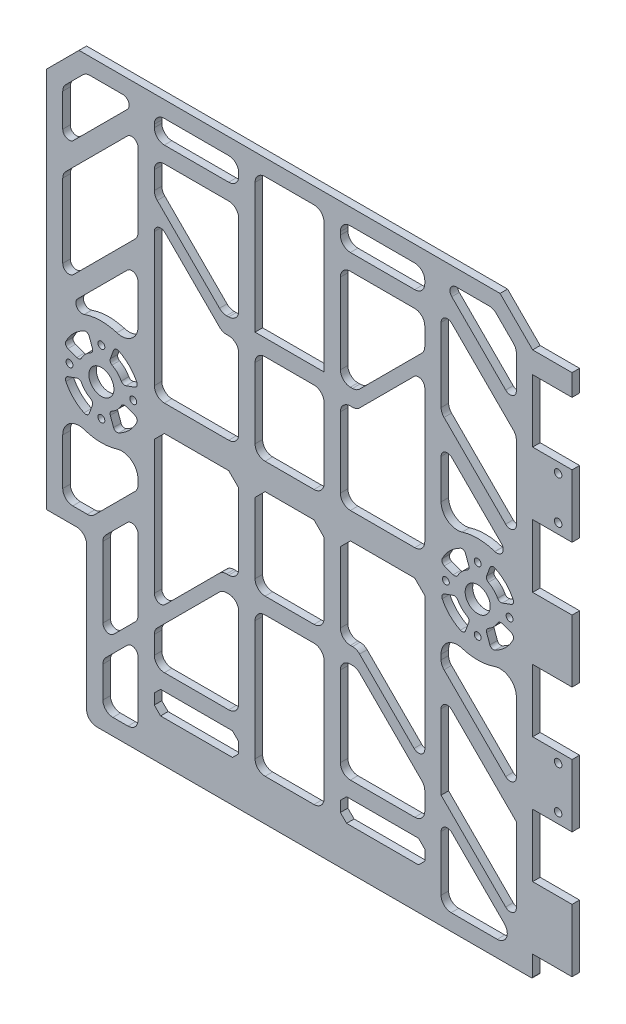
SolidWorks part; units mm, degrees
material "Liga 1060"
ref_plane "Plano frontal" through (0, 0, 0) normal (0, 0, 1) x (1, 0, 0)
ref_plane "Plano superior" through (0, 0, 0) normal (0, 1, 0) x (1, 0, 0)
ref_plane "Plano direito" through (0, 0, 0) normal (1, 0, 0) x (0, 0, -1)
sketch "Esboço1" plane through (0, 0, 0) normal (0, 0, 1) x (1, 0, 0)
  line L1 (0, 0) -> (387.6, 0)
  line L2 (0, 0) -> (0, 480)
  line L3 (0, 480) -> (387.6, 480)
  line L4 (387.6, 0) -> (387.6, 480)
  dimension "D1" = 387.6
  dimension "D2" = 480
extrude "Ressalto-extrusão1" add sketch "Esboço1" along normal blind 6
chamfer "Chanfro1" distance 26 angle 45 2 edges at (0, 480, 3) (387.6, 480, 3)
sketch "Esboço2" plane through (0, 0, 6) normal (0, 0, 1) x (1, 0, 0)
  line L0 (43.8, 260) -> (343.8, 260) construction
  line L1 (193.8, 260) -> (193.8, 0) construction
  line L2 (0, 0) -> (387.6, 0) construction
  circle A0 centre (43.8, 260) radius 10
  circle A1 centre (343.8, 260) radius 10
  dimension "D1" = 20
  dimension "D2" = 20
  dimension "D3" = 260
  dimension "D4" = 300
extrude "Corte-extrusão1" cut sketch "Esboço2" against normal through all
sketch "Esboço3" plane through (0, 0, 6) normal (0, 0, 1) x (1, 0, 0)
  circle A0 centre (43.8, 260) radius 25.4 construction
  circle A1 centre (343.8, 260) radius 25.4 construction
  circle A4 centre (43.8, 285.4) radius 2.75
  circle A5 centre (69.2, 260) radius 2.75
  circle A6 centre (43.8, 234.6) radius 2.75
  circle A7 centre (18.4, 260) radius 2.75
  circle A8 centre (343.8, 285.4) radius 2.75
  circle A9 centre (369.2, 260) radius 2.75
  circle A10 centre (343.8, 234.6) radius 2.75
  circle A11 centre (318.4, 260) radius 2.75
  point P17 (43.8, 260)
  point P25 (343.8, 260)
  dimension "D1" = 50.8
  dimension "D2" = 5.5
  dimension "D4" = 5.5
  dimension "D3" = 4
  dimension "D5" = 4
extrude "Corte-extrusão2" cut sketch "Esboço3" against normal blind 10
sketch "Esboço5" plane through (0, 0, 6) normal (0, 0, 1) x (1, 0, 0)
  line L2 (43.8, 260) -> (43.8, 285.4) construction
  line L3 (43.8, 260) -> (18.4, 260) construction
  line L10 (193.8, 480) -> (193.8, 0) construction
  line L11 (361.6, 480) -> (26, 480) construction
  line L12 (0, 0) -> (387.6, 0) construction
  line L13 (73.4003, 270.7736) -> (60.7145, 266.1564)
  line L14 (54.5736, 289.6003) -> (49.9564, 276.9145)
  line L23 (14.1997, 270.7736) -> (26.8855, 266.1564)
  line L24 (33.0264, 289.6003) -> (37.6436, 276.9145)
  line L25 (54.5736, 230.3997) -> (49.9564, 243.0855)
  line L26 (73.4003, 249.2264) -> (60.7145, 253.8436)
  line L27 (14.1997, 249.2264) -> (26.8855, 253.8436)
  line L28 (33.0264, 230.3997) -> (37.6436, 243.0855)
  line L29 (343.8, 260) -> (369.2, 260) construction
  line L30 (343.8, 260) -> (343.8, 285.4) construction
  line L31 (354.5736, 230.3997) -> (349.9564, 243.0855)
  line L32 (373.4003, 249.2264) -> (360.7145, 253.8436)
  line L33 (314.1997, 249.2264) -> (326.8855, 253.8436)
  line L34 (333.0264, 230.3997) -> (337.6436, 243.0855)
  line L35 (354.5736, 289.6003) -> (349.9564, 276.9145)
  line L36 (373.4003, 270.7736) -> (360.7145, 266.1564)
  line L37 (333.0264, 289.6003) -> (337.6436, 276.9145)
  line L38 (314.1997, 270.7736) -> (326.8855, 266.1564)
  arc A3 (37.6436, 276.9145) -> (26.8855, 266.1564) centre (43.8, 260) ccw
  arc A4 (33.0264, 289.6003) -> (14.1997, 270.7736) centre (43.8, 260) ccw
  arc A17 (60.7145, 266.1564) -> (49.9564, 276.9145) centre (43.8, 260) ccw
  arc A18 (73.4003, 270.7736) -> (54.5736, 289.6003) centre (43.8, 260) ccw
  arc A19 (49.9564, 243.0855) -> (60.7145, 253.8436) centre (43.8, 260) ccw
  arc A20 (54.5736, 230.3997) -> (73.4003, 249.2264) centre (43.8, 260) ccw
  arc A21 (26.8855, 253.8436) -> (37.6436, 243.0855) centre (43.8, 260) ccw
  arc A22 (14.1997, 249.2264) -> (33.0264, 230.3997) centre (43.8, 260) ccw
  arc A23 (373.4003, 249.2264) -> (354.5736, 230.3997) centre (343.8, 260) cw
  arc A24 (360.7145, 253.8436) -> (349.9564, 243.0855) centre (343.8, 260) cw
  arc A25 (333.0264, 230.3997) -> (314.1997, 249.2264) centre (343.8, 260) cw
  arc A26 (337.6436, 243.0855) -> (326.8855, 253.8436) centre (343.8, 260) cw
  arc A27 (314.1997, 270.7736) -> (333.0264, 289.6003) centre (343.8, 260) cw
  arc A28 (326.8855, 266.1564) -> (337.6436, 276.9145) centre (343.8, 260) cw
  arc A29 (354.5736, 289.6003) -> (373.4003, 270.7736) centre (343.8, 260) cw
  arc A30 (349.9564, 276.9145) -> (360.7145, 266.1564) centre (343.8, 260) cw
  point P28 (43.8, 260)
  point P31 (43.8, 260)
  point P48 (343.8, 260)
  point P49 (343.8, 260)
  dimension "D1" = 20
  dimension "D2" = 20
  dimension "D3" = 18
  dimension "D4" = 31.5
  dimension "D5" = 4
extrude "Corte-extrusão3" cut sketch "Esboço5" against normal through all
fillet "Filete1" radius 3 32 edges at (60.7145, 253.8436, 3) (49.9564, 243.0855, 3) (54.5736, 230.3997, 3) (73.4003, 249.2264, 3) (37.6436, 276.9145, 3) (33.0264, 289.6003, 3) (14.1997, 270.7736, 3) (26.8855, 266.1564, 3) (37.6436, 243.0855, 3) (26.8855, 253.8436, 3) (14.1997, 249.2264, 3) (33.0264, 230.3997, 3) (60.7145, 266.1564, 3) (73.4003, 270.7736, 3) (54.5736, 289.6003, 3) (49.9564, 276.9145, 3) (349.9564, 276.9145, 3) (354.5736, 289.6003, 3) (360.7145, 253.8436, 3) (349.9564, 243.0855, 3) (354.5736, 230.3997, 3) (360.7145, 266.1564, 3) (373.4003, 270.7736, 3) (373.4003, 249.2264, 3) (337.6436, 243.0855, 3) (333.0264, 230.3997, 3) (314.1997, 249.2264, 3) (326.8855, 253.8436, 3) (326.8855, 266.1564, 3) (337.6436, 276.9145, 3) (333.0264, 289.6003, 3) (314.1997, 270.7736, 3)
sketch "Esboço8" plane through (0, 0, 6) normal (0, 0, 1) x (1, 0, 0)
  text T0 "         SENAI\r\nMATO GROSSO" font "@Adobe Gothic Std B" height 40
extrude "Corte-extrusão5" [suppressed] cut sketch "Esboço8" against normal through all
sketch "Esboço11" plane through (0, 0, 0) normal (0, 0, -1) x (-1, 0, 0)
  line L0 (0, 454) -> (0, 0) construction
  line L1 (0, 150) -> (-32, 150)
  line L2 (0, 150) -> (0, 0)
  line L3 (0, 0) -> (-32, 0)
  line L4 (-32, 150) -> (-32, 0)
  line L5 (0, 0) -> (-387.6, 0) construction
  dimension "D1" = 32
  dimension "D2" = 150
extrude "Corte-extrusão6" cut sketch "Esboço11" against normal through all contours L4 L3 L2 L1
sketch "Esboço12" plane through (0, 0, 0) normal (0, 0, -1) x (-1, 0, 0)
  line L0 (-387.6, 0) -> (-387.6, 454) construction
  line L1 (-32, 0) -> (-387.6, 0)
  line L2 (-32, 0) -> (-32, 20)
  line L3 (-32, 20) -> (-387.6, 20)
  line L4 (-387.6, 0) -> (-387.6, 20)
  dimension "D1" = 20
extrude "Corte-extrusão7" cut sketch "Esboço12" against normal through all
fillet "Filete2" radius 8 2 edges at (32, 150, 3) (32, 20, 3)
sketch "Esboço13" plane through (0, 0, 6) normal (0, 0, 1) x (1, 0, 0)
  line L22 (193.8, 480) -> (193.8, 20) construction
  line L23 (361.6, 480) -> (26, 480) construction
  line L25 (40, 20) -> (387.6, 20) construction
  line L28 (314.6, 33) -> (314.6, 229.8113)
  line L30 (374.6, 33) -> (314.6, 33)
  line L31 (374.6, 231.4455) -> (374.6, 33)
  line L32 (314.6, 467) -> (356.2152, 467)
  line L33 (314.6, 290.1887) -> (314.6, 467)
  line L34 (374.6, 448.6152) -> (374.6, 288.5545)
  line L35 (356.2152, 467) -> (374.6, 448.6152)
  line L41 (387.6, 20) -> (387.6, 454) construction
  line L42 (387.6, 454) -> (361.6, 480) construction
  line L43 (13, 231.4455) -> (13, 163)
  line L44 (45, 33) -> (73, 33)
  line L45 (73, 33) -> (73, 229.8113)
  line L46 (13, 448.6152) -> (13, 288.5545)
  line L47 (31.3848, 467) -> (13, 448.6152)
  line L48 (73, 467) -> (31.3848, 467)
  line L49 (73, 290.1887) -> (73, 467)
  line L50 (13, 163) -> (45, 163)
  line L51 (45, 163) -> (45, 33)
  line L52 (32, 142) -> (32, 28) construction
  line L65 (0, 150) -> (24, 150) construction
  arc A2 (374.6, 231.4455) -> (314.6, 229.8113) centre (343.8, 260) cw
  arc A3 (374.6, 288.5545) -> (314.6, 290.1887) centre (343.8, 260) ccw
  circle A4 centre (343.8, 260) radius 10 construction
  arc A5 (13, 231.4455) -> (73, 229.8113) centre (43.8, 260) ccw
  arc A6 (13, 288.5545) -> (73, 290.1887) centre (43.8, 260) cw
  point P34 (204.3, 480)
  point P35 (204.3, 20)
  dimension "D1" = 42
  dimension "D2" = 13
  dimension "D3" = 13
  dimension "D4" = 60
  dimension "D5" = 13
  dimension "D6" = 13
  dimension "D7" = 13
  dimension "D8" = 60
  dimension "D9" = 13
  dimension "D10" = 13
extrude "Corte-extrusão8" cut sketch "Esboço13" against normal through all
fillet "Filete3" radius 13 8 edges at (314.6, 290.1887, 3) (374.6, 288.5545, 3) (374.6, 231.4455, 3) (314.6, 229.8113, 3) (73, 290.1887, 3) (73, 229.8113, 3) (13, 231.4455, 3) (13, 288.5545, 3)
sketch "Esboço14" plane through (0, 0, 6) normal (0, 0, 1) x (1, 0, 0)
  line L0 (26, 480) -> (0, 454) construction
  line L1 (73, 467) -> (13, 407)
  line L2 (13, 448.6152) -> (13, 312.04) construction
  line L3 (18.4401, 301.4642) -> (73, 356.0241)
  line L6 (73, 312.5601) -> (73, 467) construction
  line L7 (73, 448.6152) -> (13, 388.6152)
  line L8 (13, 314.4089) -> (73, 374.4089)
  line L9 (82.1924, 457.8076) -> (22.1924, 397.8076) construction
  line L10 (9.2477, 310.6566) -> (63.8076, 365.2165) construction
  line L11 (73, 467) -> (73, 448.6152)
  line L12 (13, 407) -> (13, 388.6152)
  line L13 (73, 374.4089) -> (73, 356.0241)
  line L14 (193.8, 480) -> (193.8, 20) construction
  line L15 (361.6, 480) -> (26, 480) construction
  line L16 (40, 20) -> (387.6, 20) construction
  line L17 (314.6, 374.4089) -> (314.6, 356.0241)
  line L18 (374.6, 407) -> (374.6, 388.6152)
  line L19 (314.6, 467) -> (314.6, 448.6152)
  line L20 (374.6, 314.4089) -> (314.6, 374.4089)
  line L21 (314.6, 448.6152) -> (374.6, 388.6152)
  line L22 (369.1599, 301.4642) -> (314.6, 356.0241)
  line L23 (314.6, 467) -> (374.6, 407)
  arc A0 (13, 312.04) -> (30.2073, 299.7396) centre (26, 312.04) ccw construction
  arc A1 (13, 314.4089) -> (18.4401, 301.4642) centre (25.8067, 312.1755) ccw
  arc A2 (374.6, 314.4089) -> (369.1599, 301.4642) centre (361.7933, 312.1755) cw
  dimension "D1" = 13
extrude "Ressalto-extrusão2" add sketch "Esboço14" against normal through all contours L1 L12 L7 L11 | L8 A1 L3 L13 | L23 L19 L21 L18 | A2 L20 L17 L22
sketch "Esboço15" plane through (0, 0, 6) normal (0, 0, 1) x (1, 0, 0)
  line L0 (86, 435.6152) -> (86, 409.9152)
  line L1 (86, 409.9152) -> (140.3, 355.6152)
  line L2 (140.3, 355.6152) -> (153.3, 355.6152)
  line L3 (153.3, 355.6152) -> (153.3, 435.6152)
  line L4 (153.3, 435.6152) -> (86, 435.6152)
  line L5 (86, 396.9152) -> (140.3, 342.6152)
  line L6 (140.3, 342.6152) -> (153.3, 342.6152)
  line L7 (153.3, 342.6152) -> (153.3, 270.5)
  line L8 (153.3, 270.5) -> (86, 270.5)
  line L9 (86, 270.5) -> (86, 396.9152)
  line L10 (86, 448.6152) -> (86, 467)
  line L11 (86, 467) -> (153.3, 467)
  line L12 (153.3, 467) -> (153.3, 448.6152)
  line L13 (153.3, 448.6152) -> (86, 448.6152)
  line L15 (166.3, 467) -> (221.3, 467)
  line L16 (166.3, 467) -> (166.3, 270.5)
  line L17 (166.3, 270.5) -> (221.3, 270.5)
  line L18 (221.3, 467) -> (221.3, 270.5)
  line L32 (193.8, 480) -> (193.8, 467) construction
  line L33 (361.6, 480) -> (26, 480) construction
  line L34 (73, 374.4089) -> (73, 448.6152) construction
  line L35 (69.2, 260) -> (318.4, 260) construction
  line L36 (234.3, 448.6152) -> (301.6, 448.6152)
  line L37 (234.3, 467) -> (234.3, 448.6152)
  line L38 (301.6, 467) -> (234.3, 467)
  line L39 (301.6, 448.6152) -> (301.6, 467)
  line L40 (301.6, 270.5) -> (301.6, 396.9152)
  line L41 (234.3, 270.5) -> (301.6, 270.5)
  line L42 (234.3, 342.6152) -> (234.3, 270.5)
  line L43 (247.3, 342.6152) -> (234.3, 342.6152)
  line L44 (301.6, 396.9152) -> (247.3, 342.6152)
  line L45 (234.3, 435.6152) -> (301.6, 435.6152)
  line L46 (234.3, 355.6152) -> (234.3, 435.6152)
  line L47 (247.3, 355.6152) -> (234.3, 355.6152)
  line L48 (301.6, 409.9152) -> (247.3, 355.6152)
  line L49 (301.6, 435.6152) -> (301.6, 409.9152)
  line L50 (193.8, 40) -> (193.8, 53) construction
  line L51 (301.6, 84.3848) -> (301.6, 110.0848)
  line L52 (301.6, 110.0848) -> (247.3, 164.3848)
  line L53 (247.3, 164.3848) -> (234.3, 164.3848)
  line L54 (234.3, 164.3848) -> (234.3, 84.3848)
  line L55 (234.3, 84.3848) -> (301.6, 84.3848)
  line L56 (301.6, 123.0848) -> (247.3, 177.3848)
  line L57 (247.3, 177.3848) -> (234.3, 177.3848)
  line L58 (234.3, 177.3848) -> (234.3, 249.5)
  line L59 (234.3, 249.5) -> (301.6, 249.5)
  line L60 (301.6, 249.5) -> (301.6, 123.0848)
  line L61 (301.6, 71.3848) -> (301.6, 53)
  line L62 (301.6, 53) -> (234.3, 53)
  line L63 (234.3, 53) -> (234.3, 71.3848)
  line L64 (234.3, 71.3848) -> (301.6, 71.3848)
  line L65 (221.3, 53) -> (221.3, 249.5)
  line L66 (166.3, 249.5) -> (221.3, 249.5)
  line L67 (166.3, 53) -> (166.3, 249.5)
  line L68 (166.3, 53) -> (221.3, 53)
  line L69 (153.3, 71.3848) -> (86, 71.3848)
  line L70 (153.3, 53) -> (153.3, 71.3848)
  line L71 (86, 53) -> (153.3, 53)
  line L72 (86, 71.3848) -> (86, 53)
  line L73 (86, 249.5) -> (86, 123.0848)
  line L74 (153.3, 249.5) -> (86, 249.5)
  line L75 (153.3, 177.3848) -> (153.3, 249.5)
  line L76 (140.3, 177.3848) -> (153.3, 177.3848)
  line L77 (86, 123.0848) -> (140.3, 177.3848)
  line L78 (153.3, 84.3848) -> (86, 84.3848)
  line L79 (153.3, 164.3848) -> (153.3, 84.3848)
  line L80 (140.3, 164.3848) -> (153.3, 164.3848)
  line L81 (86, 110.0848) -> (140.3, 164.3848)
  line L82 (86, 84.3848) -> (86, 110.0848)
  dimension "D1" = 55
  dimension "D2" = 13
  dimension "D3" = 13
  dimension "D4" = 13
  dimension "D5" = 13
  dimension "D6" = 135
  dimension "D7" = 13
  dimension "D8" = 13
  dimension "D9" = 13
  dimension "D10" = 80
  dimension "D11" = 21
extrude "Corte-extrusão9" cut sketch "Esboço15" against normal through all
sketch "Esboço16" plane through (0, 0, 6) normal (0, 0, 1) x (1, 0, 0)
  line L0 (166.3, 467) -> (166.3, 270.5) construction
  line L1 (166.3, 355.6152) -> (221.3, 355.6152)
  line L2 (166.3, 355.6152) -> (166.3, 342.6152)
  line L3 (166.3, 342.6152) -> (221.3, 342.6152)
  line L4 (221.3, 355.6152) -> (221.3, 342.6152)
  line L5 (221.3, 270.5) -> (221.3, 467) construction
  line L6 (234.3, 355.6152) -> (247.3, 355.6152) construction
  line L7 (247.3, 342.6152) -> (234.3, 342.6152) construction
extrude "Ressalto-extrusão3" add sketch "Esboço16" against normal through all
fillet "Filete4" radius 8 38 edges at (301.6, 270.5, 3) (234.3, 270.5, 3) (221.3, 270.5, 3) (166.3, 270.5, 3) (153.3, 270.5, 3) (86, 270.5, 3) (356.2152, 467, 3) (374.6, 448.6152, 3) (374.6, 388.6152, 3) (314.6, 374.4089, 3) (234.3, 355.6152, 3) (247.3, 355.6152, 3) (153.3, 355.6152, 3) (140.3, 355.6152, 3) (73, 374.4089, 3) (13, 388.6152, 3) (13, 448.6152, 3) (31.3848, 467, 3) (301.6, 467, 3) (234.3, 467, 3) (221.3, 467, 3) (166.3, 467, 3) (86, 467, 3) (153.3, 467, 3) (153.3, 448.6152, 3) (86, 448.6152, 3) (86, 409.9152, 3) (301.6, 409.9152, 3) (301.6, 435.6152, 3) (234.3, 435.6152, 3) (86, 435.6152, 3) (153.3, 435.6152, 3) (234.3, 342.6152, 3) (221.3, 342.6152, 3) (166.3, 342.6152, 3) (153.3, 342.6152, 3) (234.3, 448.6152, 3) (301.6, 448.6152, 3)
fillet "Filete5" radius 8 2 edges at (247.3, 342.6152, 3) (140.3, 342.6152, 3)
fillet "Filete6" radius 5 14 edges at (301.6, 396.9152, 3) (314.6, 356.0241, 3) (369.1599, 301.4642, 3) (374.6, 314.4089, 3) (314.6, 448.6152, 3) (374.6, 407, 3) (314.6, 467, 3) (73, 448.6152, 3) (73, 356.0241, 3) (18.4401, 301.4642, 3) (13, 314.4089, 3) (13, 407, 3) (73, 467, 3) (86, 396.9152, 3)
fillet "Filete7" radius 1 1 edges at (387.6, 20, 3)
sketch "Esboço17" plane through (0, 0, 6) normal (0, 0, 1) x (1, 0, 0)
  line L0 (35.8076, 163) -> (73, 200.1924)
  line L1 (13, 163) -> (45, 163) construction
  line L2 (73, 33) -> (73, 207.4399) construction
  line L3 (45, 153.8076) -> (73, 181.8076)
  line L4 (45, 163) -> (45, 33) construction
  line L5 (73, 181.8076) -> (73, 200.1924)
  line L6 (45, 153.8076) -> (45, 163)
  line L7 (45, 163) -> (35.8076, 163)
  line L8 (73, 110.0848) -> (45, 82.0848)
  line L9 (73, 97.0848) -> (45, 69.0848)
  line L10 (45, 69.0848) -> (45, 82.0848)
  line L11 (73, 97.0848) -> (73, 110.0848)
  line L12 (140.3, 164.3848) -> (86, 110.0848) construction
  line L13 (86, 123.0848) -> (140.3, 177.3848) construction
  line L14 (193.8, 249.5) -> (193.8, 53) construction
  line L15 (221.3, 249.5) -> (166.3, 249.5) construction
  line L16 (166.3, 53) -> (221.3, 53) construction
  line L17 (314.6, 97.0848) -> (314.6, 110.0848)
  line L19 (314.6, 97.0848) -> (342.6, 69.0848)
  line L20 (314.6, 110.0848) -> (342.6, 82.0848)
  line L23 (314.6, 181.8076) -> (314.6, 200.1924)
  line L24 (342.6, 153.8076) -> (314.6, 181.8076)
  line L25 (351.7924, 163) -> (314.6, 200.1924)
  line L26 (342.6, 69.0848) -> (374.6, 37.0848)
  line L27 (374.6, 33) -> (374.6, 207.96) construction
  line L28 (374.6, 37.0848) -> (374.6, 50.0848)
  line L29 (374.6, 50.0848) -> (342.6, 82.0848)
  line L30 (342.6, 153.8076) -> (374.6, 121.8076)
  line L31 (374.6, 121.8076) -> (374.6, 140.1924)
  line L32 (374.6, 140.1924) -> (351.7924, 163)
  dimension "D1" = 135
  dimension "D2" = 13
extrude "Ressalto-extrusão4" add sketch "Esboço17" against normal through all
sketch "Esboço18" plane through (0, 0, 6) normal (0, 0, 1) x (1, 0, 0)
  line L4 (166.3, 249.5) -> (166.3, 53) construction
  line L6 (166.3, 177.3848) -> (221.3, 177.3848)
  line L7 (166.3, 177.3848) -> (166.3, 164.3848)
  line L8 (166.3, 164.3848) -> (221.3, 164.3848)
  line L9 (221.3, 177.3848) -> (221.3, 164.3848)
  line L10 (221.3, 53) -> (221.3, 249.5) construction
  line L11 (247.3, 164.3848) -> (234.3, 164.3848) construction
  line L12 (234.3, 177.3848) -> (247.3, 177.3848) construction
extrude "Ressalto-extrusão5" add sketch "Esboço18" against normal through all
chamfer "Chanfro2" distance 8 angle 45 6 edges at (301.6, 249.5, 3) (234.3, 249.5, 3) (166.3, 249.5, 3) (221.3, 249.5, 3) (153.3, 249.5, 3) (86, 249.5, 3)
fillet "Filete8" radius 5 9 edges at (73, 97.0848, 3) (314.6, 97.0848, 3) (374.6, 50.0848, 3) (374.6, 140.1924, 3) (314.6, 181.8076, 3) (301.6, 123.0848, 3) (86, 123.0848, 3) (45, 82.0848, 3) (73, 181.8076, 3)
fillet "Filete9" radius 8 30 edges at (314.6, 33, 3) (45, 33, 3) (73, 33, 3) (45, 69.0848, 3) (301.6, 84.3848, 3) (234.3, 84.3848, 3) (73, 200.1924, 3) (35.8076, 163, 3) (13, 163, 3) (314.6, 200.1924, 3) (73, 110.0848, 3) (45, 153.8076, 3) (301.6, 110.0848, 3) (86, 110.0848, 3) (86, 84.3848, 3) (153.3, 84.3848, 3) (221.3, 53, 3) (166.3, 53, 3) (140.3, 177.3848, 3) (153.3, 177.3848, 3) (166.3, 177.3848, 3) (166.3, 164.3848, 3) (221.3, 164.3848, 3) (221.3, 177.3848, 3) (234.3, 177.3848, 3) (247.3, 177.3848, 3) (234.3, 164.3848, 3) (153.3, 164.3848, 3) (140.3, 164.3848, 3) (247.3, 164.3848, 3)
fillet "Filete10" radius 8 4 edges at (374.6, 37.0848, 3) (374.6, 35.0424, 0) (374.6, 33, 3) (374.6, 35.0424, 6)
chamfer "Chanfro3" distance 5 angle 45 8 edges at (86, 53, 3) (234.3, 53, 3) (301.6, 53, 3) (153.3, 53, 3) (153.3, 71.3848, 3) (301.6, 71.3848, 3) (234.3, 71.3848, 3) (86, 71.3848, 3)
ref_plane "Plano1" through (193.8, 0, 0) normal (-1, 0, 0) x (0, 0, 1)
sketch "Esboço19" plane through (387.6, 0, 0) normal (1, 0, 0) x (0, 0, -1)
  line L0 (-6, 386.903) -> (0, 386.903)
  line L1 (-6, 386.903) -> (-6, 336.8635)
  line L2 (0, 386.903) -> (0, 336.8635)
  line L3 (-6, 336.8635) -> (0, 336.8635)
  line L4 (-6, 21) -> (-6, 454) construction
  line L5 (0, 21) -> (0, 454) construction
  line L6 (-6, 136.903) -> (-6, 186.903)
  line L7 (-6, 136.903) -> (0, 136.903)
  line L8 (-6, 186.903) -> (0, 186.903)
  line L9 (0, 136.903) -> (0, 186.903)
  line L10 (-6, 286.6325) -> (-6, 236.903)
  line L11 (-6, 286.6325) -> (0, 286.6325)
  line L12 (-6, 236.903) -> (0, 236.903)
  line L13 (0, 286.6325) -> (0, 236.903)
  line L14 (-6, 436.903) -> (-6, 454)
  line L15 (-6, 436.903) -> (0, 436.903)
  line L16 (-6, 454) -> (0, 454)
  line L17 (0, 436.903) -> (0, 454)
  line L18 (0, 454) -> (-6, 454) construction
  line L19 (-6, 454) -> (-6, 480) construction
  line L20 (-6, 86.903) -> (-6, 36.903)
  line L21 (-6, 86.903) -> (0, 86.903)
  line L22 (-6, 36.903) -> (0, 36.903)
  line L23 (0, 86.903) -> (0, 36.903)
extrude "Ressalto-extrusão6" add sketch "Esboço19" along normal blind 31.4
sketch "Esboço21" plane through (0, 0, 0) normal (0, 0, -1) x (-1, 0, 0)
  circle A0 centre (-407.9, 378.903) radius 3
  circle A1 centre (-407.9, 344.903) radius 3
  circle A2 centre (20.3, 378.903) radius 3
  circle A3 centre (20.3, 344.903) radius 3
  circle A4 centre (20.3, 168.453) radius 3
  circle A5 centre (-407.9, 178.903) radius 3
  circle A6 centre (-407.9, 144.903) radius 3
extrude "Corte-extrusão11" cut sketch "Esboço21" against normal through all
